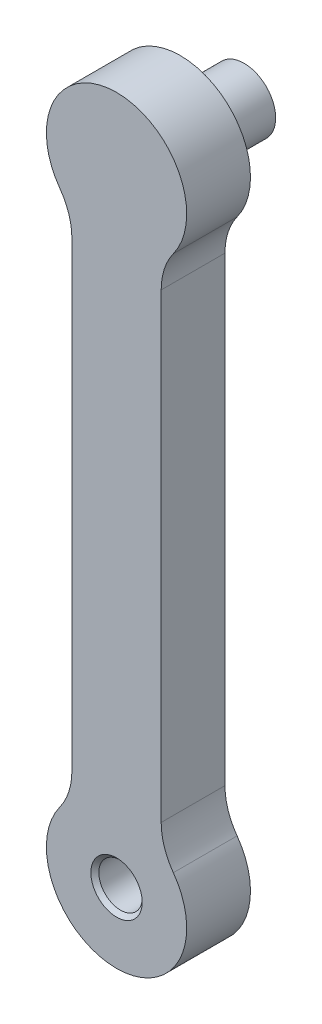
SolidWorks part; units mm, degrees
ref_plane "Plan de face" through (0, 0, 0) normal (0, 0, 1) x (1, 0, 0)
ref_plane "Plan de dessus" through (0, 0, 0) normal (0, 1, 0) x (1, 0, 0)
ref_plane "Plan de droite" through (0, 0, 0) normal (1, 0, 0) x (0, 0, -1)
sketch "Esquisse1" plane through (0, 0, 0) normal (0, 0, 1) x (1, 0, 0)
  line L0 (0, 21.7205) -> (0, -6.0998) construction
  line L1 (-7, 40) -> (-7, -40)
  line L2 (7, 40) -> (7, -40)
  line L3 (-8.714, 0) -> (6.1966, 0) construction
  arc A0 (7, 40) -> (-7, 40) centre (0, 48.4853) ccw
  arc A1 (7, -40) -> (-7, -40) centre (0, -48.4853) cw
  dimension "D3" = 11
  dimension "D1" = 80
  dimension "D2" = 14
extrude "Boss.-Extru.2" add sketch "Esquisse1" along normal blind 10
sketch "Esquisse2" plane through (0, 0, 0) normal (0, 0, -1) x (-1, 0, 0)
  circle A0 centre (0, 48.4853) radius 4.95
  arc A1 (7, 40) -> (-7, 40) centre (0, 48.4853) ccw construction
  dimension "D1" = 9.9
extrude "Boss.-Extru.3" add sketch "Esquisse2" along normal blind 10
fillet "Congé1" radius 10 4 edges at (7, 40, 5) (7, -40, 5) (-7, -40, 5) (-7, 40, 5)
sketch "Esquisse5" plane through (0, 0, 10) normal (0, 0, 1) x (1, 0, 0)
  point P0 (0, -48.4853)
hole_wizard "Trou taraudé M81" positions "Esquisse5" profile "Esquisse4" tap size "M8" standard "ISO" end condition through all
sketch "Esquisse4" plane through (0, -48.4853, 10) normal (1, 0, 0) x (0, -1, 0)
  line L0 (0, 0) -> (0, 20)
  line L1 (0, 20) -> (3.4, 20)
  line L2 (3.4, 20) -> (3.4, 0.625)
  line L3 (3.4, 0.625) -> (4.025, 0)
  line L5 (4.025, 0) -> (0, 0)
  line L6 (-3.4, 0.625) -> (-4.025, 0) construction
  line L11 (0, -6.35) -> (0, 107.95) construction
  dimension "Diamètre du trou pour taraudage jusqu'au prochain" = 6.8
  dimension "Profondeur du trou pour taraudage jusqu'au prochain" = 20
  dimension "Diamètre du fraisage entrant" = 8.05
  dimension "Angle du fraisage entrant" = 90
cosmetic thread "Filetage de perçage1" parameters "D2"=8
equation "\"L2\"= 80mm"
equation "\"D1@Esquisse1\"=\"L2\""
